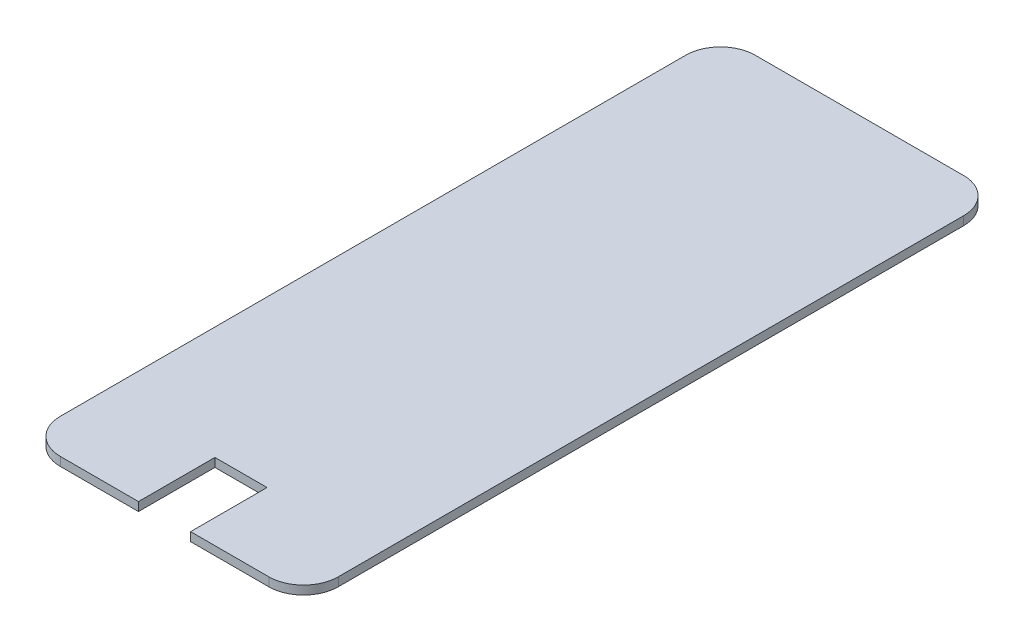
SolidWorks part; units mm, degrees
material "Thornel Mat VMA"
ref_plane "Front Plane" through (0, 0, 0) normal (0, 0, 1) x (1, 0, 0)
ref_plane "Top Plane" through (0, 0, 0) normal (0, 1, 0) x (1, 0, 0)
ref_plane "Right Plane" through (0, 0, 0) normal (1, 0, 0) x (0, 0, -1)
sketch "Sketch1" plane through (0, 0, 0) normal (0, 1, 0) x (1, 0, 0)
  line L0 (-177.8, 127) -> (177.8, 127) construction
  line L1 (-50.8, 127) -> (50.8, 127)
  line L2 (-50.8, 127) -> (-50.8, -127)
  line L3 (-50.8, -127) -> (50.8, -127)
  line L4 (50.8, 127) -> (50.8, -127)
  line L5 (-177.8, -127) -> (177.8, -127) construction
  point P8 (-50.8, 0)
  point P12 (0, -127)
  dimension "D1" = 127
  dimension "D2" = 127
  dimension "D3" = 101.6
  dimension "D4" = 254
extrude "Boss-Extrude1" add sketch "Sketch1" along normal blind 3.175
fillet "Fillet1" radius 12.7 4 edges at (-50.8, 1.5875, 127) (50.8, 1.5875, 127) (50.8, 1.5875, -127) (-50.8, 1.5875, -127)
sketch "Sketch2" plane through (0, 3.175, 0) normal (0, 1, 0) x (1, 0, 0)
  line L1 (-9.525, -99.06) -> (9.525, -99.06)
  line L2 (-9.525, -99.06) -> (-9.525, -127)
  line L3 (-9.525, -127) -> (9.525, -127)
  line L4 (9.525, -99.06) -> (9.525, -127)
  line L5 (-9.525, -99.06) -> (9.525, -127) construction
  line L6 (-9.525, -127) -> (9.525, -99.06) construction
  line L7 (-38.1, -127) -> (38.1, -127) construction
  point P0 (0, -113.03)
  point P5 (0, 0)
  point P6 (0, 0)
  point P9 (0, 0)
  dimension "D1" = 0
extrude "Cut-Extrude1" cut sketch "Sketch2" against normal through all
ref_axis "Axis1" through (0, 0, 0) along (0, 0.025, -0.9997)
